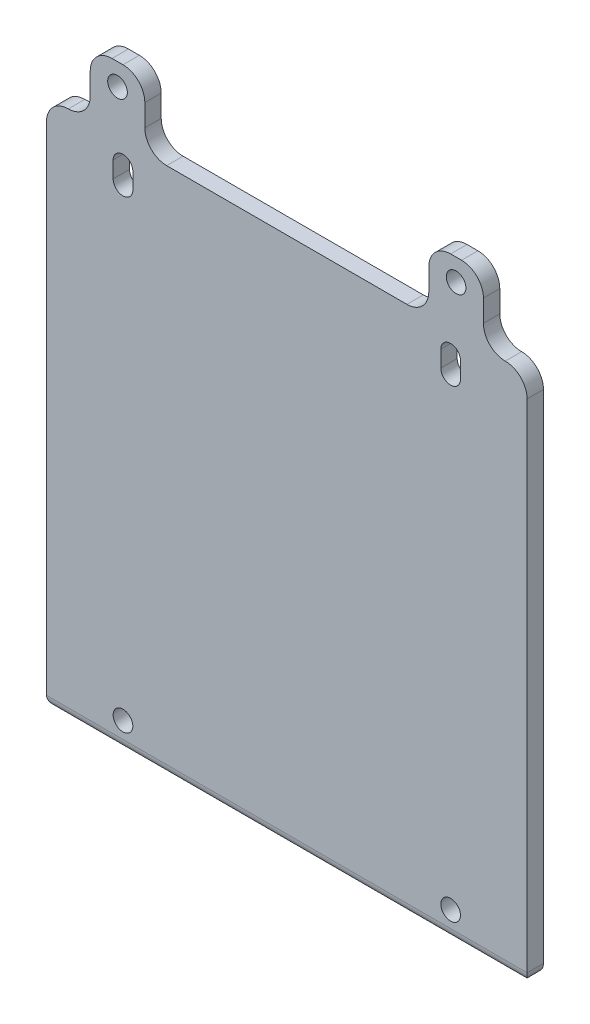
SolidWorks part; units mm, degrees
material "PLA 100% Infill"
ref_plane "Front Plane" through (0, 0, 0) normal (0, 0, 1) x (1, 0, 0)
ref_plane "Top Plane" through (0, 0, 0) normal (0, 1, 0) x (1, 0, 0)
ref_plane "Right Plane" through (0, 0, 0) normal (1, 0, 0) x (0, 0, -1)
sketch "Sketch1" plane through (0, 0, 0) normal (0, 0, 1) x (1, 0, 0)
  line L0 (-44, 97) -> (-44, 0) construction
  line L1 (0, 0) -> (-88, 0)
  line L2 (0, 0) -> (0, 97)
  line L3 (0, 97) -> (-88, 97)
  line L4 (-88, 0) -> (-88, 97)
  line L5 (-75, 105) -> (-13, 105) construction
  line L6 (-88, 97) -> (-70, 97)
  line L8 (-80, 109) -> (-70, 109)
  line L9 (-70, 97) -> (-70, 109)
  line L10 (0, 97) -> (-18, 97)
  line L12 (-8, 109) -> (-18, 109)
  line L13 (-18, 97) -> (-18, 109)
  line L14 (-75, 109) -> (-75, 105) construction
  line L15 (-80, 109) -> (-80, 97)
  line L16 (-75.8, 93) -> (-75.8, 90)
  line L17 (-8, 109) -> (-8, 97)
  line L18 (-13, 109) -> (-13, 105) construction
  line L19 (-72.2, 90) -> (-72.2, 93)
  line L20 (-15.8, 90) -> (-15.8, 93)
  line L21 (-12.2, 93) -> (-12.2, 90)
  circle A0 centre (-74, 5) radius 1.8
  circle A1 centre (-14, 5) radius 1.8
  circle A2 centre (-14, 91.5) radius 1.8
  circle A3 centre (-74, 91.5) radius 1.8
  circle A4 centre (-75, 105) radius 1.8
  circle A5 centre (-13, 105) radius 1.8
  arc A6 (-75.8, 90) -> (-72.2, 90) centre (-74, 90) ccw
  arc A7 (-72.2, 93) -> (-75.8, 93) centre (-74, 93) ccw
  arc A8 (-12.2, 90) -> (-15.8, 90) centre (-14, 90) cw
  arc A9 (-15.8, 93) -> (-12.2, 93) centre (-14, 93) cw
  dimension "D5" = 3.6
  dimension "D8" = 86.5
  dimension "D9" = 10
  dimension "D10" = 12
  dimension "D4" = 5
  dimension "D11" = 62
  dimension "D12" = 62
  dimension "D15" = 8
  dimension "D1" = 88
  dimension "D2" = 97
  dimension "D3" = 60
  dimension "D13" = 1.5
  dimension "D14" = 3
  dimension "D6" = 2
  dimension "D7" = 2
extrude "Boss-Extrude1" add sketch "Sketch1" along normal blind 3 contours L3 L9 L8 A4 | L4 L1 L2 L3 A3 A2 A1 A0 | L13 L3 L12 A5 region at (-44, 48.3916, 0) region at (-13, 102.8146, 0) region at (-75, 102.8146, 0)
fillet "Fillet1" radius 4 10 edges at (0, 97, 1.5) (-8, 97, 1.5) (-8, 109, 1.5) (-18, 109, 1.5) (-18, 97, 1.5) (-70, 97, 1.5) (-70, 109, 1.5) (-88, 97, 1.5) (-80, 109, 1.5) (-80, 97, 1.5)
fillet "Fillet2" radius 2 3 edges at (0, 0, 1.5) (-44, 0, 3) (-88, 0, 1.5)
